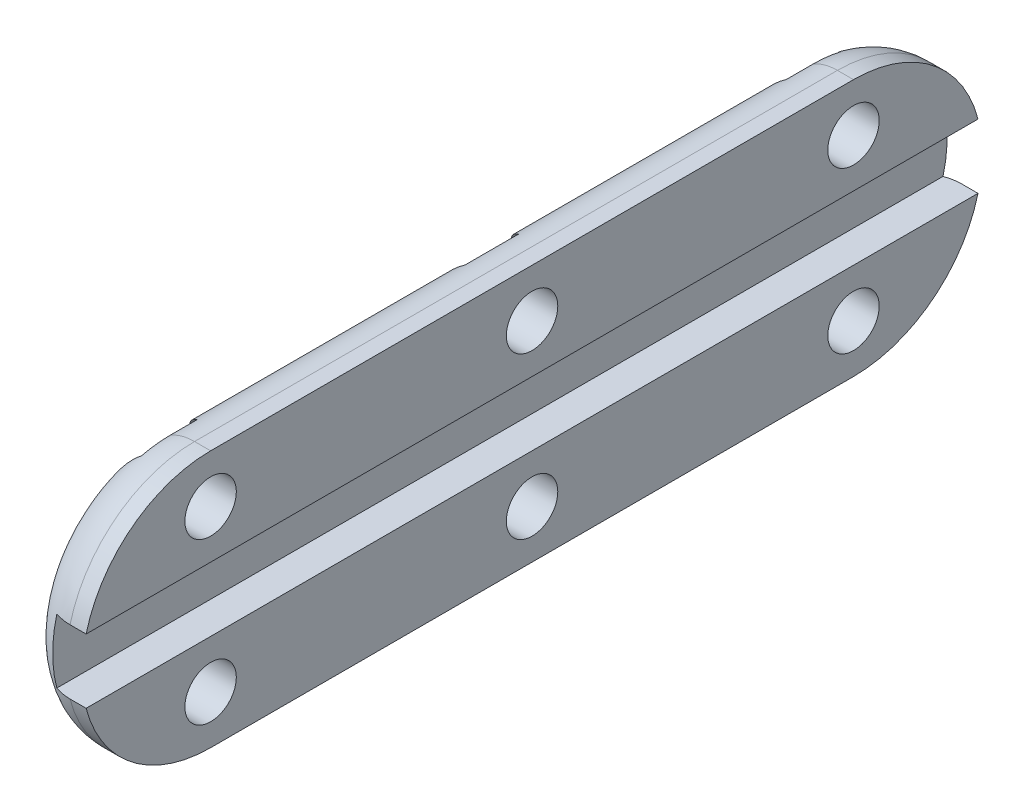
SolidWorks part; units mm, degrees
ref_plane "Front Plane" through (0, 0, 0) normal (0, 0, 1) x (1, 0, 0)
ref_plane "Top Plane" through (0, 0, 0) normal (0, 1, 0) x (1, 0, 0)
ref_plane "Right Plane" through (0, 0, 0) normal (1, 0, 0) x (0, 0, -1)
sketch "Sketch1" plane through (0, 0, 0) normal (1, 0, 0) x (0, 0, -1)
  line L0 (0, 8) -> (0, -8) construction
  line L1 (0, -8) -> (40, -8)
  line L2 (40, -8) -> (40, 8) construction
  line L3 (40, 8) -> (0, 8)
  arc A0 (0, 8) -> (0, -8) centre (0, 0) ccw
  arc A1 (40, 8) -> (40, -8) centre (40, 0) cw
  point P3 (0, 0)
  dimension "D1" = 16
  dimension "D2" = 40
extrude "Boss-Extrude1" add sketch "Sketch1" against normal blind 4
sketch "Sketch2" plane through (0, 0, 0) normal (0, 0, 1) x (1, 0, 0)
  line L0 (0, -8) -> (0, 8) construction
  line L1 (0, 2) -> (-2, 2)
  line L2 (0, 2) -> (0, -2)
  line L3 (0, -2) -> (-2, -2)
  line L4 (-2, 2) -> (-2, -2)
  point P6 (0, 0)
  dimension "D1" = 4
  dimension "D2" = 2
extrude "Cut-Extrude1" cut sketch "Sketch2" against normal through all both and the other way through all
sketch "Sketch3" plane through (0, 0, 0) normal (1, 0, 0) x (0, 0, -1)
  line L0 (0, 5) -> (40, 5) construction
  line L1 (0, 8) -> (0, -8) construction
  line L2 (40, -8) -> (40, 8) construction
  line L3 (0, -5) -> (40, -5) construction
  line L4 (40, 8) -> (0, 8) construction
  line L6 (0, -8) -> (40, -8) construction
  circle A0 centre (0, 5) radius 1.6
  circle A1 centre (40, 5) radius 1.6
  circle A2 centre (40, -5) radius 1.6
  circle A3 centre (0, -5) radius 1.6
  circle A4 centre (20, 5) radius 1.6
  circle A5 centre (20, -5) radius 1.6
  dimension "D3" = 3.2
  dimension "D1" = 3
  dimension "D2" = 3
extrude "Cut-Extrude2" cut sketch "Sketch3" against normal up to next
fillet "Fillet1" radius 3 4 edges at (-4, -8, -20) (-4, 0, 8) (-4, 8, -20) (-4, 0, -48)
sketch "Sketch4" plane through (-4, 0, 0) normal (-1, 0, 0) x (0, 0, 1)
  line L0 (0, 8) -> (0, -8) construction
  line L1 (-36.8246, 5) -> (-38.4123, 7.75)
  line L2 (-38.4123, 7.75) -> (-41.5877, 7.75)
  line L3 (-41.5877, 7.75) -> (-43.1754, 5)
  line L4 (-43.1754, 5) -> (-41.5877, 2.25)
  line L5 (-41.5877, 2.25) -> (-38.4123, 2.25)
  line L6 (-38.4123, 2.25) -> (-36.8246, 5)
  line L7 (-3.1754, 5) -> (-1.5877, 2.25)
  line L8 (-1.5877, 2.25) -> (1.5877, 2.25)
  line L9 (1.5877, 2.25) -> (3.1754, 5)
  line L10 (3.1754, 5) -> (1.5877, 7.75)
  line L11 (1.5877, 7.75) -> (-1.5877, 7.75)
  line L12 (-1.5877, 7.75) -> (-3.1754, 5)
  line L13 (0, 5) -> (-40, 5) construction
  line L14 (-3.1754, -5) -> (-1.5877, -7.75)
  line L15 (-1.5877, -7.75) -> (1.5877, -7.75)
  line L16 (1.5877, -7.75) -> (3.1754, -5)
  line L17 (3.1754, -5) -> (1.5877, -2.25)
  line L18 (1.5877, -2.25) -> (-1.5877, -2.25)
  line L19 (-1.5877, -2.25) -> (-3.1754, -5)
  line L20 (-36.8246, -5) -> (-38.4123, -2.25)
  line L21 (-38.4123, -2.25) -> (-41.5877, -2.25)
  line L22 (-41.5877, -2.25) -> (-43.1754, -5)
  line L23 (-43.1754, -5) -> (-41.5877, -7.75)
  line L24 (-41.5877, -7.75) -> (-38.4123, -7.75)
  line L25 (-38.4123, -7.75) -> (-36.8246, -5)
  line L26 (0, -5) -> (-40, -5) construction
  line L28 (-16.8246, 5) -> (-18.4123, 7.75)
  line L29 (-18.4123, 7.75) -> (-21.5877, 7.75)
  line L30 (-21.5877, 7.75) -> (-23.1754, 5)
  line L31 (-23.1754, 5) -> (-21.5877, 2.25)
  line L32 (-21.5877, 2.25) -> (-18.4123, 2.25)
  line L33 (-18.4123, 2.25) -> (-16.8246, 5)
  line L34 (-16.8246, -5) -> (-18.4123, -2.25)
  line L35 (-18.4123, -2.25) -> (-21.5877, -2.25)
  line L36 (-21.5877, -2.25) -> (-23.1754, -5)
  line L37 (-23.1754, -5) -> (-21.5877, -7.75)
  line L38 (-21.5877, -7.75) -> (-18.4123, -7.75)
  line L39 (-18.4123, -7.75) -> (-16.8246, -5)
  circle A0 centre (-40, 5) radius 2.75 construction
  circle A1 centre (0, 5) radius 2.75 construction
  circle A2 centre (0, -5) radius 2.75 construction
  circle A3 centre (-40, -5) radius 2.75 construction
  circle A4 centre (-20, 5) radius 2.75 construction
  circle A5 centre (-20, -5) radius 2.75 construction
  point P51 (0, 0)
  point P60 (0, 0)
  dimension "D1" = 5.5
  dimension "D2" = 5.5
  dimension "D3" = 5.5
  dimension "D4" = 5.5
extrude "Cut-Extrude3" cut sketch "Sketch4" against normal blind 1.5
